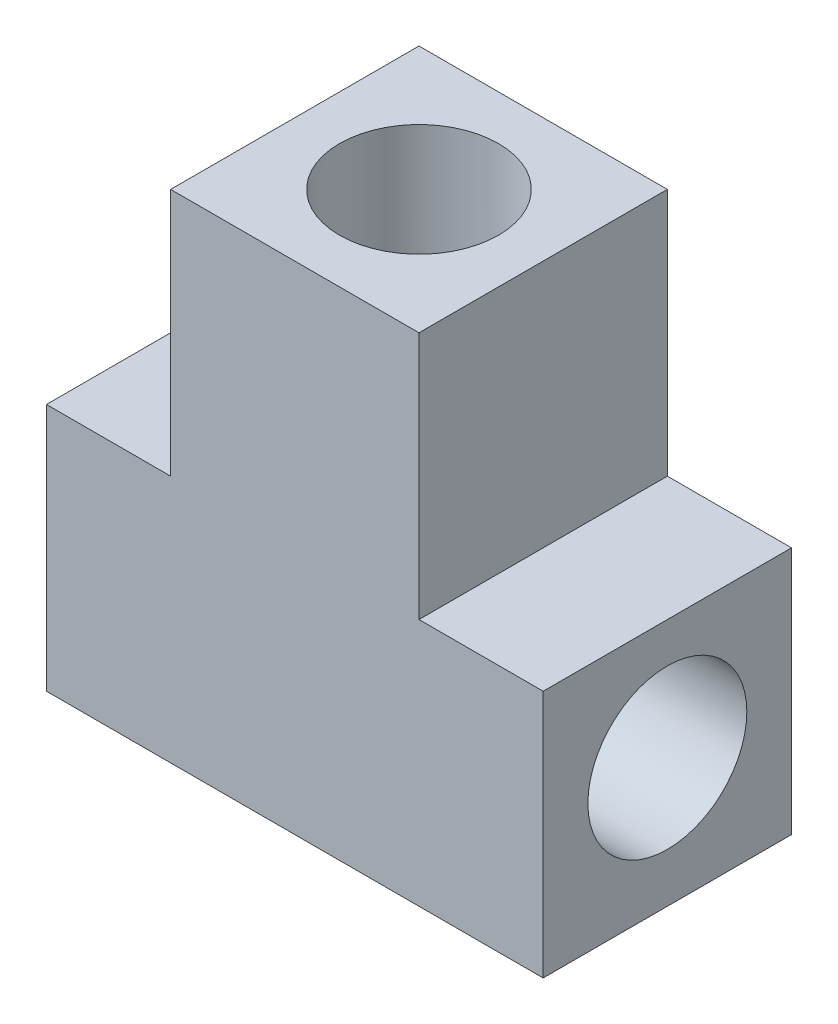
SolidWorks part; units mm, degrees
ref_plane "Alzado" through (0, 0, 0) normal (0, 0, 1) x (1, 0, 0)
ref_plane "Planta" through (0, 0, 0) normal (0, 1, 0) x (1, 0, 0)
ref_plane "Vista lateral" through (0, 0, 0) normal (1, 0, 0) x (0, 0, -1)
sketch "Croquis2" plane through (0, 0, 0) normal (0, 1, 0) x (1, 0, 0)
  line L1 (-25, -12.5) -> (25, -12.5)
  line L2 (-25, -12.5) -> (-25, 12.5)
  line L3 (-25, 12.5) -> (25, 12.5)
  line L4 (25, -12.5) -> (25, 12.5)
  line L5 (-25, -12.5) -> (25, 12.5) construction
  line L6 (-25, 12.5) -> (25, -12.5) construction
  point P0 (0, 0)
  dimension "D1" = 50
  dimension "D2" = 25
extrude "Saliente-Extruir2" add sketch "Croquis2" along normal blind 25
sketch "Croquis9" plane through (0, 0, 0) normal (0, 1, 0) x (1, 0, 0)
  line L1 (-12.5, -12.5) -> (12.5, -12.5)
  line L2 (-12.5, -12.5) -> (-12.5, 12.5)
  line L3 (-12.5, 12.5) -> (12.5, 12.5)
  line L4 (12.5, -12.5) -> (12.5, 12.5)
  line L5 (-12.5, -12.5) -> (12.5, 12.5) construction
  line L6 (-12.5, 12.5) -> (12.5, -12.5) construction
  point P0 (0, 0)
  dimension "D1" = 25
  dimension "D2" = 25
extrude "Saliente-Extruir3" add sketch "Croquis9" along normal blind 50 contours L2 L1 L4 L3
sketch "Croquis10" plane through (0, 0, 0) normal (1, 0, 0) x (0, 0, -1)
  circle A0 centre (0, 12.9573) radius 8
  dimension "D1" = 16
extrude "Cortar-Extruir2" cut sketch "Croquis10" along normal blind 43 and the other way blind 49
sketch "Croquis11" plane through (0, 50, 0) normal (0, 1, 0) x (1, 0, 0)
  circle A0 centre (0, 0) radius 8
  dimension "D1" = 16
extrude "Cortar-Extruir3" cut sketch "Croquis11" against normal mid plane 75
